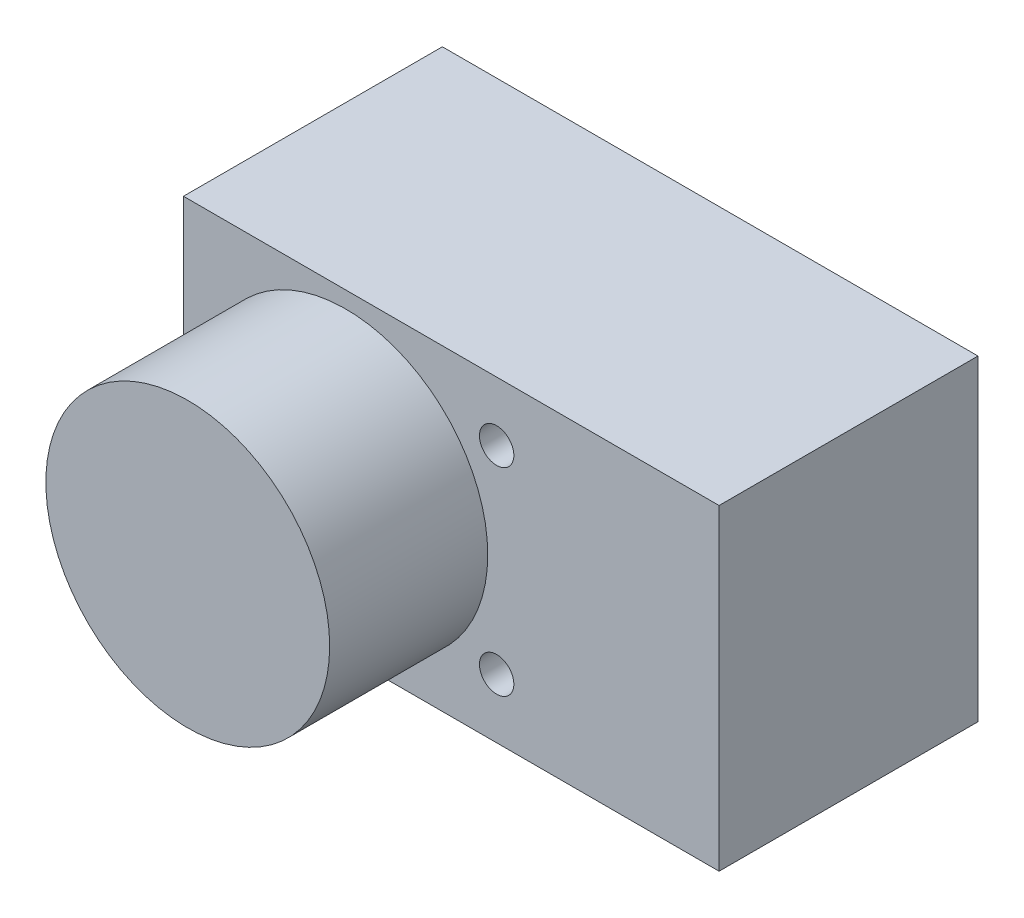
SolidWorks part; units mm, degrees
ref_plane "Front Plane" through (0, 0, 0) normal (0, 0, 1) x (1, 0, 0)
ref_plane "Top Plane" through (0, 0, 0) normal (0, 1, 0) x (1, 0, 0)
ref_plane "Right Plane" through (0, 0, 0) normal (1, 0, 0) x (0, 0, -1)
sketch "Sketch1" plane through (0, 0, 0) normal (0, 0, 1) x (1, 0, 0)
  line L1 (0, 0) -> (45.8724, 0)
  line L2 (0, 0) -> (0, 27.1272)
  line L3 (0, 27.1272) -> (45.8724, 27.1272)
  line L4 (45.8724, 0) -> (45.8724, 27.1272)
  dimension "D1" = 45.8724
  dimension "D2" = 27.1272
extrude "Boss-Extrude1" add sketch "Sketch1" along normal blind 22.1742
sketch "Sketch2" plane through (0, 0, 22.1742) normal (0, 0, 1) x (1, 0, 0)
  line L0 (0, 27.1272) -> (0, 0) construction
  line L2 (0, 13.5636) -> (45.8724, 13.5636) construction
  line L3 (45.8724, 0) -> (45.8724, 27.1272) construction
  circle A0 centre (13.9065, 13.5636) radius 12.1539
  dimension "D1" = 24.3078
  dimension "D2" = 13.9065
  dimension "D3" = 0
extrude "Boss-Extrude2" add sketch "Sketch2" along normal blind 13.5382
sketch "Sketch3" plane through (0, 0, 0) normal (0, 0, -1) x (-1, 0, 0)
  line L0 (-45.8724, 13.5636) -> (0, 13.5636) construction
  line L1 (-45.8724, 0) -> (-45.8724, 27.1272) construction
  line L2 (0, 27.1272) -> (0, 0) construction
  circle A0 centre (-11.2522, 13.5636) radius 8.9662
  dimension "D2" = 17.9324
  dimension "D3" = 11.2522
extrude "Boss-Extrude3" add sketch "Sketch3" along normal blind 1.2954 contours A0
sketch "Sketch4" plane through (0, 0, -1.2954) normal (0, 0, -1) x (-1, 0, 0)
  line L0 (-13.791, 15.8496) -> (-8.7134, 15.8496)
  line L1 (-45.8724, 13.5636) -> (0, 13.5636) construction
  line L2 (-45.8724, 0) -> (-45.8724, 27.1272) construction
  line L3 (0, 27.1272) -> (0, 0) construction
  line L4 (-13.791, 11.2776) -> (-8.7134, 11.2776)
  circle A0 centre (-11.2522, 13.5636) radius 8.9662 construction
  circle A1 centre (-11.2522, 13.5636) radius 8.9662 construction
  circle A2 centre (-11.2522, 13.5636) radius 3.4163
  dimension "D1" = 6.8326
  dimension "D2" = 2.286
extrude "Boss-Extrude4" add sketch "Sketch4" along normal blind 5.715 contours L0 A2 L4 region at (11.2522, 13.5636, -1.2954)
sketch "Sketch5" plane through (0, 0, 0) normal (0, 0, -1) x (-1, 0, 0)
  line L0 (0, 0) -> (-45.8724, 0) construction
  line L1 (-45.8724, 27.1272) -> (0, 27.1272) construction
  line L2 (-45.8724, 0) -> (-45.8724, 27.1272) construction
  point P0 (-26.8224, 22.0472)
  point P1 (-26.8224, 5.08)
  dimension "D1" = 5.08
  dimension "D2" = 5.08
  dimension "D3" = 19.05
  dimension "D4" = 0
hole_wizard "#32 (0.116) Diameter Hole1" positions "Sketch6" profile "Sketch7" hole size "#32" standard "ANSI Inch" end condition through all
sketch "Sketch6" plane through (0, 0, 0) normal (0, 0, -1) x (-1, 0, 0)
  point P0 (-26.8224, 22.0472)
  point P3 (-26.8224, 5.08)
sketch "Sketch7" plane through (26.8224, 22.0472, 0) normal (1, 0, 0) x (0, 1, 0)
  line L0 (0, 0) -> (0, 35.7124)
  line L1 (0, 35.7124) -> (1.4732, 35.7124)
  line L2 (1.4732, 35.7124) -> (1.4732, 0)
  line L5 (1.4732, 0) -> (0, 0)
  line L11 (0, -6.35) -> (0, 107.95) construction
  dimension "Thru Hole Dia." = 2.9464
  dimension "Thru Hole Depth" = 35.7124
sketch "Sketch8" plane through (0, 0, -1.2954) normal (0, 0, -1) x (-1, 0, 0)
  circle A0 centre (-26.8224, 5.08) radius 1.4732 construction
  circle A1 centre (-26.8224, 22.0472) radius 1.4732 construction
  circle A2 centre (-11.2522, 13.5636) radius 8.9662 construction
  circle A3 centre (-26.8224, 5.08) radius 1.4732
  circle A4 centre (-26.8224, 22.0472) radius 1.4732
  circle A5 centre (-11.2522, 13.5636) radius 8.9662
  dimension "D1" = 15.5702
  dimension "D2" = 8.4836
equation "\"height\"= 0.051"
equation "\"diameter\"= .269"
equation "\"D1@Boss-Extrude3\"=\"height\""
equation "\"D1@Sketch4\"=\"diameter\""
equation "\"holefromwall\"= .2"
